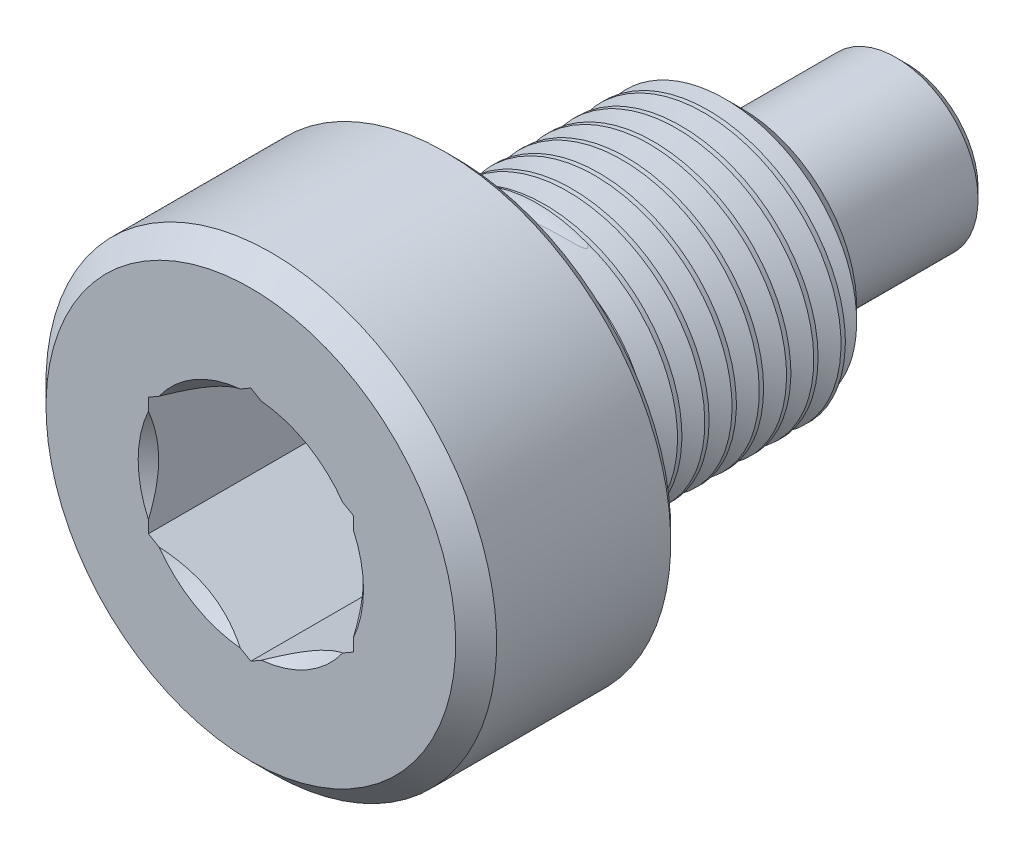
SolidWorks part; units mm, degrees
ref_plane "Front" through (0, 0, 0) normal (0, 0, 1) x (1, 0, 0)
ref_plane "Top" through (0, 0, 0) normal (0, 1, 0) x (1, 0, 0)
ref_plane "Right" through (0, 0, 0) normal (1, 0, 0) x (0, 0, -1)
sketch "Sketch1" plane through (0, 0, 0) normal (1, 0, 0) x (0, 0, -1)
  line L0 (11.0043, 0) -> (32, 0)
  line L1 (1, 11) -> (9.5, 11)
  line L2 (0.5, 5) -> (8, 5)
  line L3 (0, 5.5) -> (0, 10)
  line L4 (10, 7.4) -> (10, 10.5)
  line L5 (24.8, 4) -> (31.5, 4)
  line L6 (0, 11) -> (32, 11) construction
  line L7 (10, 0) -> (10, 11) construction
  line L8 (32, 0) -> (32, 3.5)
  line L9 (24, 4.8) -> (24, 5.575)
  line L10 (0, 10) -> (1, 11)
  line L11 (0, 4) -> (32, 4) construction
  line L12 (0, 5) -> (32, 5) construction
  line L13 (14, 6.575) -> (23, 6.575)
  line L14 (8, 0) -> (32, 0) construction
  line L15 (0, 0) -> (32, 0) construction
  line L16 (0, 0) -> (0, 11) construction
  line L17 (24, 0) -> (24, 4) construction
  line L18 (8, 6.575) -> (32, 6.575) construction
  line L19 (8, 5) -> (11.0043, 0)
  line L20 (12, 5.4) -> (12.1781, 5.4)
  line L21 (11.0043, 5.4) -> (32, 5.4) construction
  line L22 (10, 10.5) -> (9.5, 11)
  line L23 (32, 0) -> (32, 4) construction
  line L24 (31.5, 4) -> (32, 3.5)
  line L25 (24, 5.575) -> (23, 6.575)
  line L26 (0, 5.5) -> (0.5, 5)
  arc A0 (12, 5.4) -> (10, 7.4) centre (12, 7.4) cw
  arc A1 (12.1781, 5.4) -> (14, 6.575) centre (12.1781, 7.4) ccw
  arc A2 (24, 4.8) -> (24.8, 4) centre (24.8, 4.8) ccw
  point P9 (24, 6.575)
  point P15 (8, 11)
  dimension "D12" = 2
  dimension "D13" = 0.8
  dimension "D10" = 2
  dimension "D1" = 32
  dimension "D2" = 11
  dimension "D3" = 5
  dimension "D4" = 8
  dimension "D5" = 10
  dimension "D6" = 6.575
  dimension "D7" = 4
  dimension "D8" = 8
  dimension "D9" = 59
  dimension "D11" = 5.4
  dimension "D14" = 4
  dimension "D15" = 1
  dimension "D16" = 45
  dimension "D17" = 0.5
  dimension "D18" = 45
  dimension "D19" = 0.5
  dimension "D20" = 45
  dimension "D21" = 1
  dimension "D22" = 45
  dimension "D23" = 0.5
  dimension "D24" = 45
  dimension "D25" = 5.5
revolve "Revolve1" add sketch "Sketch1" angle 360 about L0
sketch "Sketch2" plane through (0, 0, 0) normal (0, 0, 1) x (1, 0, 0)
  line L1 (0, 5.7735) -> (-5, 2.8868)
  line L2 (-5, 2.8868) -> (-5, -2.8868)
  line L3 (-5, -2.8868) -> (0, -5.7735)
  line L4 (0, -5.7735) -> (5, -2.8868)
  line L5 (5, -2.8868) -> (5, 2.8868)
  line L6 (5, 2.8868) -> (0, 5.7735)
  circle A0 centre (0, 0) radius 5 construction
  dimension "D1" = 10
extrude "Cut-Extrude1" cut sketch "Sketch2" against normal blind 8
sketch "Sketch5" plane through (0, 0, -24) normal (0, 0, -1) x (-1, 0, 0)
  circle A0 centre (0, 0) radius 6.575 construction
  circle A1 centre (0, 0) radius 6.575
curve "Helix/Spiral1" pitch 1.33 height 11.33 radius 6.575 centre (0, 0, -24) axis (0, 0, 1) start towards (1, 0, 0)
sketch "Sketch6" plane through (0, 0, 0) normal (1, 0, 0) x (0, 0, -1)
  line L0 (0, 0) -> (24, 0) construction
  line L1 (24, -4.8) -> (24, 4.8) construction
  line L2 (24, 5.5) -> (23.3355, 6.7765)
  line L3 (23.3355, 6.7765) -> (24.6645, 6.7765)
  line L4 (24.6645, 6.7765) -> (24, 5.5)
  dimension "D1" = 55
  dimension "D2" = 62.5
  dimension "D3" = 62.5
  dimension "D4" = 1.329
  dimension "D5" = 5.5
sweep "Cut-Sweep4" cut profiles "Sketch6" path "Helix/Spiral1" align with end faces yes
